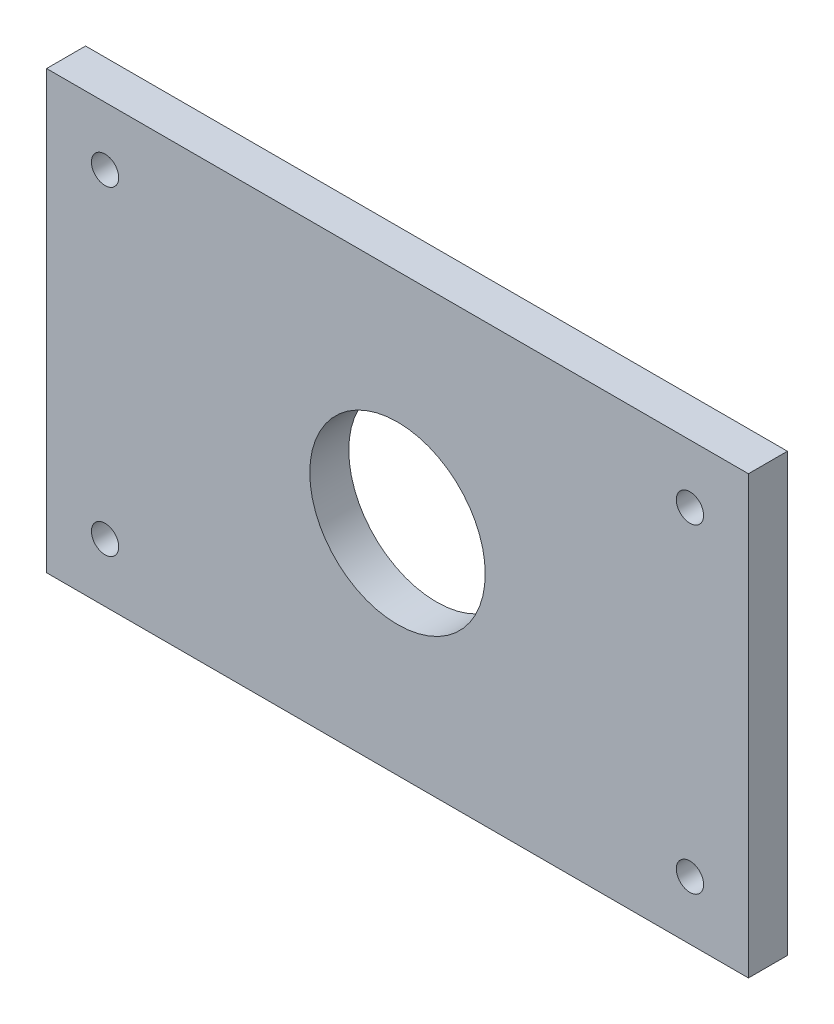
SolidWorks part; units mm, degrees
ref_plane "Front" through (0, 0, 0) normal (0, 0, 1) x (1, 0, 0)
ref_plane "Top" through (0, 0, 0) normal (0, 1, 0) x (1, 0, 0)
ref_plane "Right" through (0, 0, 0) normal (1, 0, 0) x (0, 0, -1)
sketch "ｽｹｯﾁ1" plane through (0, 0, 0) normal (0, 0, 1) x (1, 0, 0)
  line L1 (-45, -28) -> (45, -28)
  line L2 (-45, -28) -> (-45, 28)
  line L3 (-45, 28) -> (45, 28)
  line L4 (45, -28) -> (45, 28)
  line L5 (0, 28) -> (0, -28) construction
  line L6 (-45, 0) -> (45, 0) construction
  circle A0 centre (-37.5, 20.5) radius 1.75
  circle A1 centre (37.5, 20.5) radius 1.75
  circle A2 centre (37.5, -20.5) radius 1.75
  circle A3 centre (-37.5, -20.5) radius 1.75
  point P0 (0, 0)
  dimension "D1" = 75
  dimension "D2" = 75
  dimension "D3" = 3.5
  dimension "D4" = 3.5
  dimension "D5" = 41
  dimension "D6" = 3.5
  dimension "D7" = 3.5
  dimension "D10" = 7.5
  dimension "D11" = 7.5
  dimension "D12" = 7.5
  dimension "D13" = 7.5
  dimension "D14" = 7.5
  dimension "D8" = 56
  dimension "D9" = 90
extrude "ﾎﾞｽ - 押し出し1" add sketch "ｽｹｯﾁ1" along normal blind 5
sketch "ｽｹｯﾁ2" plane through (0, 0, 5) normal (0, 0, 1) x (1, 0, 0)
  circle A0 centre (0, 0) radius 11.25
  dimension "D1" = 22.5
extrude "ｶｯﾄ - 押し出し1" cut sketch "ｽｹｯﾁ2" against normal blind 5
